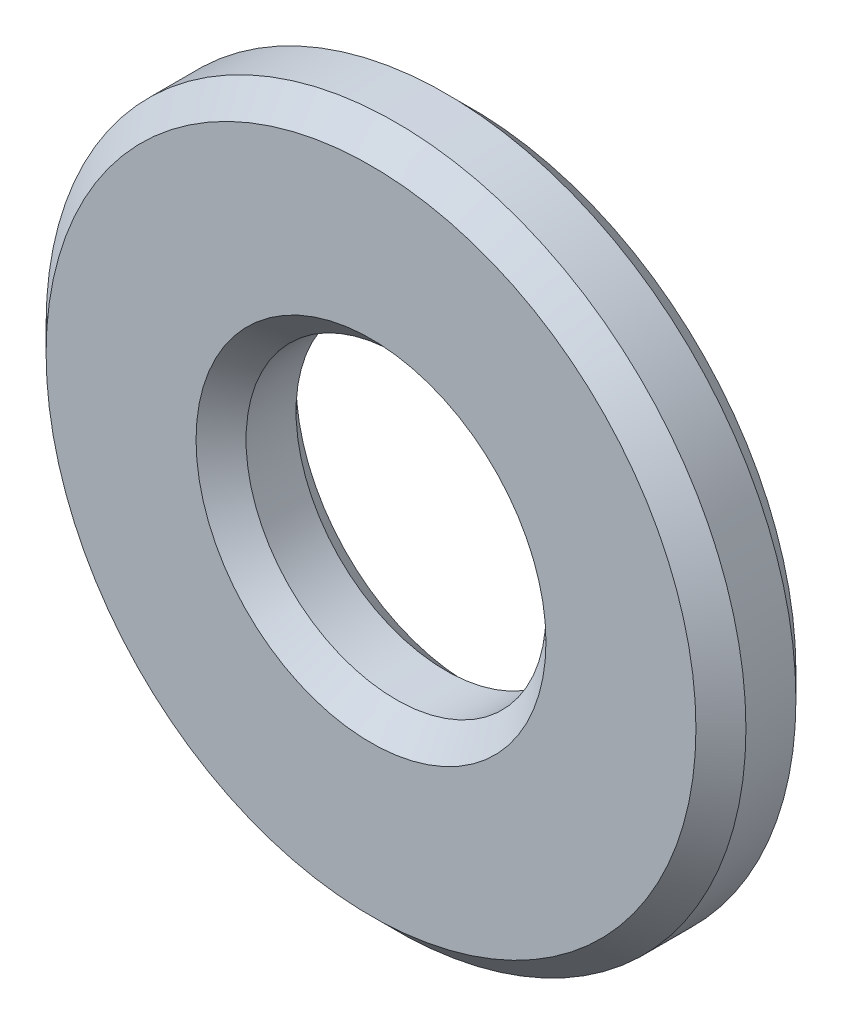
SolidWorks part; units mm, degrees
ref_plane "Front Plane" through (0, 0, 0) normal (0, 0, 1) x (1, 0, 0)
ref_plane "Top Plane" through (0, 0, 0) normal (0, 1, 0) x (1, 0, 0)
ref_plane "Right Plane" through (0, 0, 0) normal (1, 0, 0) x (0, 0, -1)
sketch "Sketch2" plane through (0, 0, 0) normal (0, 0, 1) x (1, 0, 0)
  circle A0 centre (0, 0) radius 1.5
  circle A1 centre (0, 0) radius 3.5
  dimension "D1" = 3
  dimension "D2" = 2
base flange "Base-Flange1" sketch "Sketch2" thickness 1 reverse thickness direction no parameters "D1"=0.7366
chamfer "Chamfer1" distance 0.25 angle 45 4 edges at (3.5, 0, -1) (1.5, 0, -1) (3.5, 0, 0) (1.5, 0, 0)
sketch "Bend-Lines1" [suppressed] plane through (0, 0, 0) normal (0, 1, 0) x (1, 0, 0)
sketch "Bounding-Box1" [suppressed] plane through (0, 0, 0) normal (0, 1, 0) x (1, 0, 0)
sheet metal parameters "Sheet-Metal1" thickness 1 parameters "D1"=0.7366
flat pattern "Flat-Pattern1" [suppressed]
sketch "Bend-Lines2" plane through (0, 0, 0) normal (0, 1, 0) x (1, 0, 0)
sketch3d "Bounding-Box2" [suppressed]
  line L0 (-3.5, -3.5, 0) -> (3.5, -3.5, 0) construction
  line L1 (-3.5, 3.5, 0) -> (3.5, 3.5, 0) construction
  line L2 (-3.5, -3.5, 0) -> (-3.5, 3.5, 0) construction
  line L3 (3.5, -3.5, 0) -> (3.5, 3.5, 0) construction
